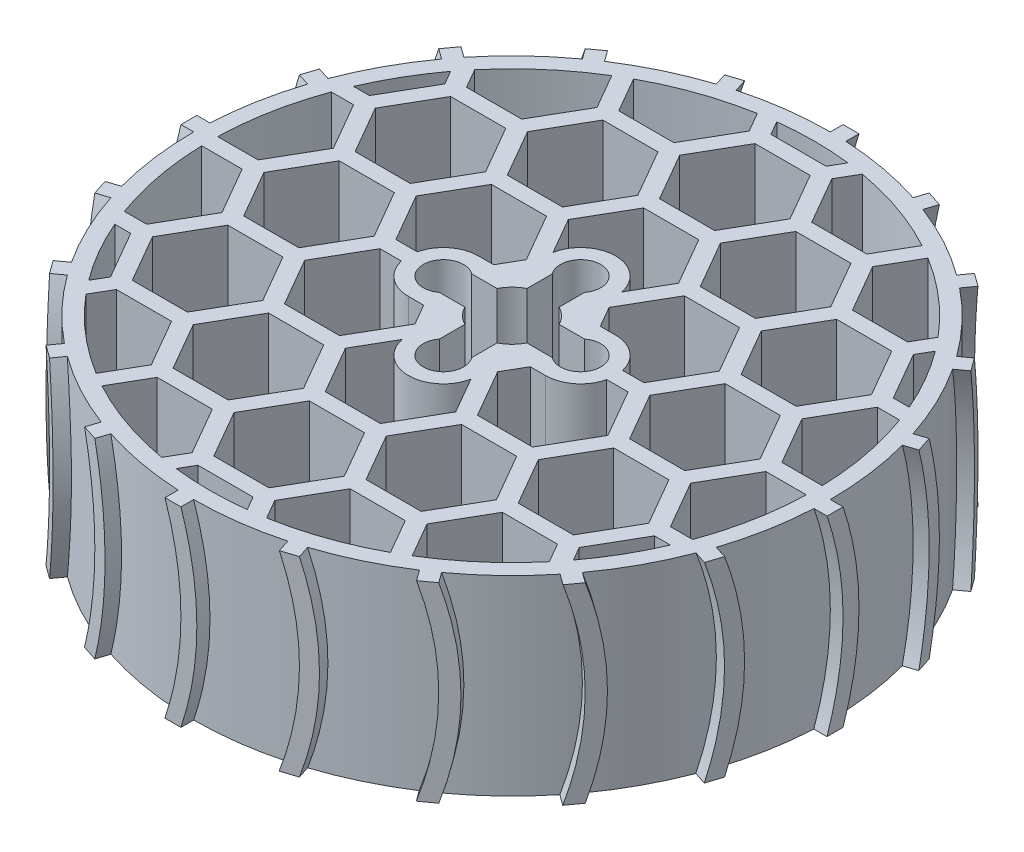
SolidWorks part; units mm, degrees
ref_plane "Front Plane" through (0, 0, 0) normal (0, 0, 1) x (1, 0, 0)
ref_plane "Top Plane" through (0, 0, 0) normal (0, 1, 0) x (1, 0, 0)
ref_plane "Right Plane" through (0, 0, 0) normal (1, 0, 0) x (0, 0, -1)
sketch "Sketch1" plane through (0, 0, 0) normal (0, 1, 0) x (1, 0, 0)
  line L0 (-17.7275, -5.0583) -> (-9.768, -5.0583)
  line L1 (-17.7275, 5.0583) -> (-9.768, 5.0583)
  line L2 (-21.548, 11) -> (-11, 11)
  line L3 (-21.548, -11) -> (-11, -11)
  line L4 (-11, 21.548) -> (-11, 11)
  line L5 (11, 21.548) -> (11, 11)
  line L6 (5.0583, 17.7275) -> (5.0583, 9.768)
  line L7 (-5.0583, 17.7275) -> (-5.0583, 9.768)
  line L8 (21.548, 11) -> (11, 11)
  line L9 (21.548, -11) -> (11, -11)
  line L10 (17.7275, -5.0583) -> (9.768, -5.0583)
  line L11 (17.7275, 5.0583) -> (9.768, 5.0583)
  line L12 (11, -21.548) -> (11, -11)
  line L13 (-11, -21.548) -> (-11, -11)
  line L14 (-5.0583, -17.7275) -> (-5.0583, -9.768)
  line L15 (5.0583, -17.7275) -> (5.0583, -9.768)
  line L16 (-21.548, 0) -> (21.548, 0) construction
  arc A0 (-9.768, -5.0583) -> (-5.0583, -9.768) centre (0, 0) ccw
  arc A1 (-21.548, 11) -> (-21.548, -11) centre (-21.548, 0) ccw
  arc A5 (-5.0583, 9.768) -> (-9.768, 5.0583) centre (0, 0) ccw
  circle A6 centre (-21.548, 0) radius 3.302
  circle A7 centre (-21.548, 0) radius 6.339
  circle A8 centre (0, 0) radius 11 construction
  arc A9 (11, 21.548) -> (-11, 21.548) centre (0, 21.548) ccw
  circle A10 centre (0, 21.548) radius 6.339
  circle A11 centre (0, 21.548) radius 3.302
  arc A12 (21.548, -11) -> (21.548, 11) centre (21.548, 0) ccw
  circle A13 centre (21.548, 0) radius 6.339
  circle A14 centre (21.548, 0) radius 3.302
  arc A15 (-11, -21.548) -> (11, -21.548) centre (0, -21.548) ccw
  circle A16 centre (0, -21.548) radius 6.339
  circle A17 centre (0, -21.548) radius 3.302
  arc A18 (-5.0583, 9.768) -> (-9.768, 5.0583) centre (0, 0) ccw
  arc A19 (9.768, 5.0583) -> (5.0583, 9.768) centre (0, 0) ccw
  arc A20 (5.0583, -9.768) -> (9.768, -5.0583) centre (0, 0) ccw
  arc A21 (-9.768, -5.0583) -> (-5.0583, -9.768) centre (0, 0) ccw
  point P60 (0, 0)
  dimension "D1" = 6.604
  dimension "D2" = 12.678
  dimension "D3" = 22
  dimension "D4" = 11
  dimension "D7" = 4
  dimension "D5" = 10.548
  dimension "D6" = 7.9595
  dimension "D8" = 21.548
  dimension "D9" = 5.0583
  dimension "D10" = 5.0583
  dimension "D11" = 10.1166
sketch "Sketch3" plane through (0, 0, 0) normal (0, 1, 0) x (1, 0, 0)
  line L0 (0, 0) -> (17.3205, 0) construction
  line L1 (8.6603, 15) -> (-8.6603, 15) construction
  line L2 (-8.6603, 15) -> (-17.3205, 0) construction
  line L3 (-17.3205, 0) -> (-8.6603, -15) construction
  line L4 (-8.6603, -15) -> (8.6603, -15) construction
  line L5 (8.6603, -15) -> (17.3205, 0) construction
  line L6 (17.3205, 0) -> (8.6603, 15) construction
  line L7 (38.9711, 32.5) -> (21.6506, 32.5)
  line L8 (21.6506, 32.5) -> (12.9904, 17.5)
  line L9 (12.9904, 17.5) -> (16.7432, 11)
  line L11 (38.9711, 2.5) -> (47.6314, 17.5)
  line L12 (47.6314, 17.5) -> (38.9711, 32.5)
  line L13 (69.282, 50) -> (51.9615, 50)
  line L14 (51.9615, 50) -> (43.3013, 35)
  line L15 (43.3013, 35) -> (51.9615, 20)
  line L16 (51.9615, 20) -> (69.282, 20)
  line L17 (69.282, 20) -> (77.9423, 35)
  line L18 (77.9423, 35) -> (69.282, 50)
  line L21 (73.6122, 52.5) -> (82.2724, 37.5)
  line L22 (82.2724, 37.5) -> (87.2855, 37.5)
  line L25 (38.9711, -2.5) -> (32.2601, -2.5)
  line L27 (12.9904, -17.5) -> (21.6506, -32.5)
  line L28 (21.6506, -32.5) -> (38.9711, -32.5)
  line L29 (38.9711, -32.5) -> (47.6314, -17.5)
  line L30 (47.6314, -17.5) -> (38.9711, -2.5)
  line L31 (69.282, 15) -> (51.9615, 15)
  line L32 (51.9615, 15) -> (43.3013, 0)
  line L33 (43.3013, 0) -> (51.9615, -15)
  line L34 (51.9615, -15) -> (69.282, -15)
  line L35 (69.282, -15) -> (77.9423, 0)
  line L36 (77.9423, 0) -> (69.282, 15)
  line L37 (89.2679, 32.5) -> (82.2724, 32.5)
  line L38 (82.2724, 32.5) -> (73.6122, 17.5)
  line L39 (73.6122, 17.5) -> (82.2724, 2.5)
  line L40 (82.2724, 2.5) -> (94.9671, 2.5)
  line L43 (38.9711, -37.5) -> (21.6506, -37.5)
  line L44 (21.6506, -37.5) -> (12.9904, -52.5)
  line L45 (12.9904, -52.5) -> (21.6506, -67.5)
  line L46 (21.6506, -67.5) -> (38.9711, -67.5)
  line L47 (38.9711, -67.5) -> (47.6314, -52.5)
  line L48 (47.6314, -52.5) -> (38.9711, -37.5)
  line L49 (69.282, -20) -> (51.9615, -20)
  line L50 (51.9615, -20) -> (43.3013, -35)
  line L51 (43.3013, -35) -> (51.9615, -50)
  line L52 (51.9615, -50) -> (69.282, -50)
  line L53 (69.282, -50) -> (77.9423, -35)
  line L54 (77.9423, -35) -> (69.282, -20)
  line L55 (94.9671, -2.5) -> (82.2724, -2.5)
  line L56 (82.2724, -2.5) -> (73.6122, -17.5)
  line L57 (73.6122, -17.5) -> (82.2724, -32.5)
  line L58 (82.2724, -32.5) -> (89.2679, -32.5)
  line L61 (38.9711, -72.5) -> (21.6506, -72.5)
  line L62 (21.6506, -72.5) -> (12.9904, -87.5)
  line L63 (12.9904, -87.5) -> (16.4881, -93.5582)
  line L66 (45.3185, -83.4939) -> (38.9711, -72.5)
  line L67 (69.282, -55) -> (51.9615, -55)
  line L68 (51.9615, -55) -> (43.3013, -70)
  line L69 (43.3013, -70) -> (49.6486, -80.9939)
  line L72 (72.7798, -61.0582) -> (69.282, -55)
  line L73 (87.2855, -37.5) -> (82.2724, -37.5)
  line L74 (82.2724, -37.5) -> (73.6122, -52.5)
  line L75 (73.6122, -52.5) -> (76.1187, -56.8414)
  line L80 (-10.7898, -23.6884) -> (-17.3205, -35)
  line L81 (-17.3205, -35) -> (-8.6603, -50)
  line L82 (-8.6603, -50) -> (8.6603, -50)
  line L83 (8.6603, -50) -> (17.3205, -35)
  line L84 (17.3205, -35) -> (10.7898, -23.6884)
  line L85 (8.6603, -55) -> (-8.6603, -55)
  line L86 (-8.6603, -55) -> (-17.3205, -70)
  line L87 (-17.3205, -70) -> (-8.6603, -85)
  line L88 (-8.6603, -85) -> (8.6603, -85)
  line L89 (8.6603, -85) -> (17.3205, -70)
  line L90 (17.3205, -70) -> (8.6603, -55)
  line L91 (8.6603, -90) -> (-8.6603, -90)
  line L92 (-8.6603, -90) -> (-11.1668, -94.3414)
  line L97 (0, 0) -> (77.9423, -45) construction
  line L98 (-21.6506, 32.5) -> (-38.9711, 32.5)
  line L99 (-38.9711, 32.5) -> (-47.6314, 17.5)
  line L100 (-47.6314, 17.5) -> (-38.9711, 2.5)
  line L101 (-38.9711, 2.5) -> (-32.2601, 2.5)
  line L103 (-12.9904, 17.5) -> (-21.6506, 32.5)
  line L104 (-51.9615, 50) -> (-69.282, 50)
  line L105 (-69.282, 50) -> (-77.9423, 35)
  line L106 (-77.9423, 35) -> (-69.282, 20)
  line L107 (-69.282, 20) -> (-51.9615, 20)
  line L108 (-51.9615, 20) -> (-43.3013, 35)
  line L109 (-43.3013, 35) -> (-51.9615, 50)
  line L113 (-87.2855, 37.5) -> (-82.2724, 37.5)
  line L114 (-82.2724, 37.5) -> (-73.6122, 52.5)
  line L115 (-73.6122, 52.5) -> (-76.1187, 56.8414)
  line L116 (-21.6506, 67.5) -> (-38.9711, 67.5)
  line L117 (-38.9711, 67.5) -> (-47.6314, 52.5)
  line L118 (-47.6314, 52.5) -> (-38.9711, 37.5)
  line L119 (-38.9711, 37.5) -> (-21.6506, 37.5)
  line L120 (-21.6506, 37.5) -> (-12.9904, 52.5)
  line L121 (-12.9904, 52.5) -> (-21.6506, 67.5)
  line L124 (-72.7798, 61.0582) -> (-69.282, 55)
  line L125 (-69.282, 55) -> (-51.9615, 55)
  line L126 (-51.9615, 55) -> (-43.3013, 70)
  line L127 (-43.3013, 70) -> (-49.6486, 80.9939)
  line L128 (-82.2724, 102.5) -> (-99.5929, 102.5) [skipped]
  line L129 (-99.5929, 102.5) -> (-108.2532, 87.5) [skipped]
  line L130 (-108.2532, 87.5) -> (-99.5929, 72.5) [skipped]
  line L131 (-99.5929, 72.5) -> (-82.2724, 72.5) [skipped]
  line L132 (-82.2724, 72.5) -> (-73.6122, 87.5) [skipped]
  line L133 (-73.6122, 87.5) -> (-82.2724, 102.5) [skipped]
  line L136 (-45.3185, 83.4939) -> (-38.9711, 72.5)
  line L137 (-38.9711, 72.5) -> (-21.6506, 72.5)
  line L138 (-21.6506, 72.5) -> (-12.9904, 87.5)
  line L139 (-12.9904, 87.5) -> (-16.4881, 93.5582)
  line L140 (-51.9615, 120) -> (-69.282, 120) [skipped]
  line L141 (-69.282, 120) -> (-77.9423, 105) [skipped]
  line L142 (-77.9423, 105) -> (-69.282, 90) [skipped]
  line L143 (-69.282, 90) -> (-51.9615, 90) [skipped]
  line L144 (-51.9615, 90) -> (-43.3013, 105) [skipped]
  line L145 (-43.3013, 105) -> (-51.9615, 120) [skipped]
  line L146 (-82.2724, 137.5) -> (-99.5929, 137.5) [skipped]
  line L147 (-99.5929, 137.5) -> (-108.2532, 122.5) [skipped]
  line L148 (-108.2532, 122.5) -> (-99.5929, 107.5) [skipped]
  line L149 (-99.5929, 107.5) -> (-82.2724, 107.5) [skipped]
  line L150 (-82.2724, 107.5) -> (-73.6122, 122.5) [skipped]
  line L151 (-73.6122, 122.5) -> (-82.2724, 137.5) [skipped]
  line L152 (-21.6506, 137.5) -> (-38.9711, 137.5) [skipped]
  line L153 (-38.9711, 137.5) -> (-47.6314, 122.5) [skipped]
  line L154 (-47.6314, 122.5) -> (-38.9711, 107.5) [skipped]
  line L155 (-38.9711, 107.5) -> (-21.6506, 107.5) [skipped]
  line L156 (-21.6506, 107.5) -> (-12.9904, 122.5) [skipped]
  line L157 (-12.9904, 122.5) -> (-21.6506, 137.5) [skipped]
  line L158 (-51.9615, 155) -> (-69.282, 155) [skipped]
  line L159 (-69.282, 155) -> (-77.9423, 140) [skipped]
  line L160 (-77.9423, 140) -> (-69.282, 125) [skipped]
  line L161 (-69.282, 125) -> (-51.9615, 125) [skipped]
  line L162 (-51.9615, 125) -> (-43.3013, 140) [skipped]
  line L163 (-43.3013, 140) -> (-51.9615, 155) [skipped]
  line L164 (-82.2724, 172.5) -> (-99.5929, 172.5) [skipped]
  line L165 (-99.5929, 172.5) -> (-108.2532, 157.5) [skipped]
  line L166 (-108.2532, 157.5) -> (-99.5929, 142.5) [skipped]
  line L167 (-99.5929, 142.5) -> (-82.2724, 142.5) [skipped]
  line L168 (-82.2724, 142.5) -> (-73.6122, 157.5) [skipped]
  line L169 (-73.6122, 157.5) -> (-82.2724, 172.5) [skipped]
  line L170 (8.6603, 50) -> (-8.6603, 50)
  line L171 (-8.6603, 50) -> (-17.3205, 35)
  line L172 (-17.3205, 35) -> (-10.7898, 23.6884)
  line L174 (10.7898, 23.6884) -> (17.3205, 35)
  line L175 (17.3205, 35) -> (8.6603, 50)
  line L176 (8.6603, 85) -> (-8.6603, 85)
  line L177 (-8.6603, 85) -> (-17.3205, 70)
  line L178 (-17.3205, 70) -> (-8.6603, 55)
  line L179 (-8.6603, 55) -> (8.6603, 55)
  line L180 (8.6603, 55) -> (17.3205, 70)
  line L181 (17.3205, 70) -> (8.6603, 85)
  line L184 (-11.1668, 94.3414) -> (-8.6603, 90)
  line L185 (-8.6603, 90) -> (8.6603, 90)
  line L186 (8.6603, 90) -> (11.1668, 94.3414)
  line L188 (0, 0) -> (-77.9423, 45) construction
  line L189 (-51.9615, 15) -> (-69.282, 15)
  line L190 (-69.282, 15) -> (-77.9423, 0)
  line L191 (-77.9423, 0) -> (-69.282, -15)
  line L192 (-69.282, -15) -> (-51.9615, -15)
  line L193 (-51.9615, -15) -> (-43.3013, 0)
  line L194 (-43.3013, 0) -> (-51.9615, 15)
  line L195 (-82.2724, -2.5) -> (-94.9671, -2.5)
  line L198 (-89.2679, -32.5) -> (-82.2724, -32.5)
  line L199 (-82.2724, -32.5) -> (-73.6122, -17.5)
  line L200 (-73.6122, -17.5) -> (-82.2724, -2.5)
  line L201 (-51.9615, -20) -> (-69.282, -20)
  line L202 (-69.282, -20) -> (-77.9423, -35)
  line L203 (-77.9423, -35) -> (-69.282, -50)
  line L204 (-69.282, -50) -> (-51.9615, -50)
  line L205 (-51.9615, -50) -> (-43.3013, -35)
  line L206 (-43.3013, -35) -> (-51.9615, -20)
  line L207 (-82.2724, -37.5) -> (-87.2855, -37.5)
  line L211 (-76.1187, -56.8414) -> (-73.6122, -52.5)
  line L212 (-73.6122, -52.5) -> (-82.2724, -37.5)
  line L213 (-51.9615, -55) -> (-69.282, -55)
  line L214 (-69.282, -55) -> (-72.7798, -61.0582)
  line L217 (-49.6486, -80.9939) -> (-43.3013, -70)
  line L218 (-43.3013, -70) -> (-51.9615, -55)
  line L219 (-82.2724, -72.5) -> (-99.5929, -72.5) [skipped]
  line L220 (-99.5929, -72.5) -> (-108.2532, -87.5) [skipped]
  line L221 (-108.2532, -87.5) -> (-99.5929, -102.5) [skipped]
  line L222 (-99.5929, -102.5) -> (-82.2724, -102.5) [skipped]
  line L224 (-73.6122, -87.5) -> (-82.2724, -72.5) [skipped]
  line L225 (-51.9615, -90) -> (-69.282, -90) [skipped]
  line L226 (-69.282, -90) -> (-77.9423, -105) [skipped]
  line L227 (-77.9423, -105) -> (-69.282, -120) [skipped]
  line L228 (-69.282, -120) -> (-51.9615, -120) [skipped]
  line L230 (-43.3013, -105) -> (-51.9615, -90) [skipped]
  line L231 (-82.2724, -107.5) -> (-99.5929, -107.5) [skipped]
  line L232 (-99.5929, -107.5) -> (-108.2532, -122.5) [skipped]
  line L233 (-108.2532, -122.5) -> (-99.5929, -137.5) [skipped]
  line L234 (-99.5929, -137.5) -> (-82.2724, -137.5) [skipped]
  line L236 (-73.6122, -122.5) -> (-82.2724, -107.5) [skipped]
  line L238 (-38.9711, -2.5) -> (-47.6314, -17.5)
  line L239 (-47.6314, -17.5) -> (-38.9711, -32.5)
  line L240 (-38.9711, -32.5) -> (-21.6506, -32.5)
  line L241 (-21.6506, -32.5) -> (-12.9904, -17.5)
  line L242 (-12.9904, -17.5) -> (-16.7432, -11)
  line L243 (-21.6506, -37.5) -> (-38.9711, -37.5)
  line L244 (-38.9711, -37.5) -> (-47.6314, -52.5)
  line L245 (-47.6314, -52.5) -> (-38.9711, -67.5)
  line L246 (-38.9711, -67.5) -> (-21.6506, -67.5)
  line L247 (-21.6506, -67.5) -> (-12.9904, -52.5)
  line L248 (-12.9904, -52.5) -> (-21.6506, -37.5)
  line L249 (-21.6506, -72.5) -> (-38.9711, -72.5)
  line L250 (-38.9711, -72.5) -> (-45.3185, -83.4939)
  line L254 (-12.9904, -87.5) -> (-21.6506, -72.5)
  line L255 (-21.6506, 32.5) -> (-51.9615, 15) construction
  line L256 (-21.6506, 32.5) -> (-21.6506, 3.3004) construction
  line L257 (-16.4881, -93.5582) -> (-12.9904, -87.5)
  line L258 (76.1187, 56.8414) -> (73.6122, 52.5)
  line L259 (8.6603, 55) -> (51.9615, 50) construction
  line L260 (-94.9671, 2.5) -> (-82.2724, 2.5)
  line L261 (-82.2724, 2.5) -> (-73.6122, 17.5)
  line L262 (-73.6122, 17.5) -> (-82.2724, 32.5)
  line L263 (-82.2724, 32.5) -> (-89.2679, 32.5)
  line L266 (60.6218, 50) -> (60.6218, 79.5299) construction
  line L267 (17.3205, 35) -> (43.3013, 70) construction
  line L269 (49.6486, 80.9939) -> (43.3013, 70)
  line L270 (43.3013, 70) -> (51.9615, 55)
  line L271 (51.9615, 55) -> (69.282, 55)
  line L272 (69.282, 55) -> (72.7798, 61.0582)
  line L274 (51.9615, 85) -> (8.6603, 90) construction
  line L275 (21.6506, 37.5) -> (38.9711, 37.5)
  line L276 (38.9711, 37.5) -> (47.6314, 52.5)
  line L277 (47.6314, 52.5) -> (38.9711, 67.5)
  line L278 (38.9711, 67.5) -> (21.6506, 67.5)
  line L279 (21.6506, 67.5) -> (12.9904, 52.5)
  line L280 (12.9904, 52.5) -> (21.6506, 37.5)
  line L281 (43.3013, 70) -> (21.3703, 99.5443) construction
  line L282 (-69.282, 50) -> (-51.9615, 20) construction
  line L285 (12.9904, 87.5) -> (21.6506, 72.5)
  line L286 (21.6506, 72.5) -> (38.9711, 72.5)
  line L287 (38.9711, 72.5) -> (45.3185, 83.4939)
  line L289 (-8.6603, 120) -> (-17.3205, 105) [skipped]
  line L290 (8.6603, 120) -> (-8.6603, 120) [skipped]
  line L291 (17.3205, 105) -> (8.6603, 120) [skipped]
  line L292 (-21.6506, 102.5) -> (-38.9711, 102.5) [skipped]
  line L293 (-47.273, 88.1207) -> (-47.6314, 87.5) [skipped]
  line L294 (-52.6783, 85) -> (-69.282, 85) [skipped]
  line L295 (-69.282, 85) -> (-77.9423, 70) [skipped]
  line L296 (-82.2724, 67.5) -> (-99.5929, 67.5) [skipped]
  line L297 (-99.5929, 67.5) -> (-108.2532, 52.5) [skipped]
  line L298 (-108.2532, 52.5) -> (-99.5929, 37.5) [skipped]
  line L299 (-103.923, 25) -> (-108.2532, 17.5) [skipped]
  line L300 (-51.9615, 50) -> (-69.282, 20) construction
  line L301 (11.1668, -94.3414) -> (8.6603, -90)
  line L302 (-99.9513, 3.1207) -> (-99.5929, 2.5) [skipped]
  line L303 (-108.2532, -17.5) -> (-99.5929, -32.5) [skipped]
  line L304 (-99.5929, -2.5) -> (-99.9513, -3.1207) [skipped]
  line L305 (-99.5929, -37.5) -> (-108.2532, -52.5) [skipped]
  line L306 (-108.2532, -52.5) -> (-99.5929, -67.5) [skipped]
  line L307 (-99.5929, -67.5) -> (-82.2724, -67.5) [skipped]
  line L308 (-77.9423, -70) -> (-69.282, -85) [skipped]
  line L309 (-52.6783, -85) -> (-51.9615, -85) [skipped]
  line L310 (-47.273, -88.1207) -> (-38.9711, -102.5) [skipped]
  line L312 (-38.9711, -102.5) -> (-21.6506, -102.5) [skipped]
  line L313 (17.3205, -105) -> (13.8753, -99.0327) [skipped]
  line L314 (8.6603, -120) -> (17.3205, -105) [skipped]
  line L315 (-8.6603, -120) -> (8.6603, -120) [skipped]
  line L316 (-17.3205, -105) -> (-8.6603, -120) [skipped]
  line L317 (21.6506, -102.5) -> (38.9711, -102.5) [skipped]
  line L318 (47.273, -88.1207) -> (47.6314, -87.5) [skipped]
  line L319 (52.6783, -85) -> (69.282, -85) [skipped]
  line L320 (69.282, -85) -> (77.9423, -70) [skipped]
  line L321 (82.2724, -67.5) -> (99.5929, -67.5) [skipped]
  line L322 (99.5929, -67.5) -> (103.923, -60) [skipped]
  line L323 (108.2532, -52.5) -> (99.5929, -37.5) [skipped]
  line L324 (99.5929, -32.5) -> (108.2532, -17.5) [skipped]
  line L325 (99.9513, -3.1207) -> (99.5929, -2.5) [skipped]
  line L326 (99.9513, 3.1207) -> (108.2532, 17.5) [skipped]
  line L327 (108.2532, 17.5) -> (99.5929, 32.5) [skipped]
  line L328 (82.2724, 67.5) -> (78.8272, 61.5327) [skipped]
  line L329 (99.5929, 67.5) -> (82.2724, 67.5) [skipped]
  line L330 (108.2532, 52.5) -> (99.5929, 67.5) [skipped]
  line L331 (99.5929, 37.5) -> (108.2532, 52.5) [skipped]
  line L332 (30.3109, 102.5) -> (21.6506, 102.5) [skipped]
  line L333 (16.4881, 93.5582) -> (12.9904, 87.5)
  line L334 (21.6506, 102.5) -> (20.5681, 100.625) [skipped]
  line L335 (47.6314, 87.5) -> (47.273, 88.1207) [skipped]
  line L336 (-17.7275, -5.0583) -> (-9.768, -5.0583)
  line L337 (69.282, 85) -> (60.6218, 85) [skipped]
  line L338 (73.6122, 77.5) -> (69.282, 85) [skipped]
  line L339 (-17.7275, 5.0583) -> (-9.768, 5.0583)
  line L340 (-21.548, 11) -> (-11, 11)
  line L341 (-21.548, -11) -> (-11, -11)
  line L342 (-11, 21.548) -> (-11, 11)
  line L343 (11, 21.548) -> (11, 11)
  line L344 (5.0583, 17.7275) -> (5.0583, 9.768)
  line L345 (-5.0583, 17.7275) -> (-5.0583, 9.768)
  line L346 (21.548, 11) -> (11, 11)
  line L347 (21.548, -11) -> (11, -11)
  line L348 (17.7275, -5.0583) -> (9.768, -5.0583)
  line L349 (17.7275, 5.0583) -> (9.768, 5.0583)
  line L350 (11, -21.548) -> (11, -11)
  line L351 (-11, -21.548) -> (-11, -11)
  line L352 (-5.0583, -17.7275) -> (-5.0583, -9.768)
  line L353 (5.0583, -17.7275) -> (5.0583, -9.768)
  line L354 (-21.548, 0) -> (21.548, 0) construction
  line L355 (-16.7432, 11) -> (-12.9904, 17.5)
  line L356 (-21.6506, 2.5) -> (-21.1983, 3.2834) [skipped]
  line L357 (-32.2601, -2.5) -> (-38.9711, -2.5)
  line L358 (-21.6506, -2.5) -> (-23.7051, -2.5) [skipped]
  line L359 (8.6603, -20) -> (6.1471, -20) [skipped]
  line L360 (16.7432, -11) -> (12.9904, -17.5)
  line L361 (21.1983, -3.2834) -> (19.6095, -6.0353) [skipped]
  line L363 (32.2601, 2.5) -> (38.9711, 2.5)
  line L364 (21.6506, 2.5) -> (23.7051, 2.5) [skipped]
  line L365 (-8.6603, 20) -> (-6.1471, 20) [skipped]
  circle A0 centre (0, 0) radius 15 construction
  circle A1 centre (0, 0) radius 100
  circle A2 centre (0, 0) radius 95
  circle A3 centre (-90.9327, 17.5) radius 15 construction
  circle A4 centre (60.6218, 70) radius 15 construction
  circle A5 centre (30.3109, 52.5) radius 15 construction
  circle A6 centre (30.3109, 87.5) radius 15 construction
  arc A7 (-9.768, -5.0583) -> (-5.0583, -9.768) centre (0, 0) ccw
  arc A8 (-21.548, 11) -> (-21.548, -11) centre (-21.548, 0) ccw
  arc A9 (-5.0583, 9.768) -> (-9.768, 5.0583) centre (0, 0) ccw
  circle A10 centre (-21.548, 0) radius 3.302
  circle A11 centre (-21.548, 0) radius 6.339
  circle A12 centre (0, 0) radius 11 construction
  arc A13 (11, 21.548) -> (-11, 21.548) centre (0, 21.548) ccw
  circle A14 centre (0, 21.548) radius 6.339
  circle A15 centre (0, 21.548) radius 3.302
  arc A16 (21.548, -11) -> (21.548, 11) centre (21.548, 0) ccw
  circle A17 centre (21.548, 0) radius 6.339
  circle A18 centre (21.548, 0) radius 3.302
  arc A19 (-11, -21.548) -> (11, -21.548) centre (0, -21.548) ccw
  circle A20 centre (0, -21.548) radius 6.339
  circle A21 centre (0, -21.548) radius 3.302
  arc A22 (-5.0583, 9.768) -> (-9.768, 5.0583) centre (0, 0) ccw
  arc A23 (9.768, 5.0583) -> (5.0583, 9.768) centre (0, 0) ccw
  arc A24 (5.0583, -9.768) -> (9.768, -5.0583) centre (0, 0) ccw
  arc A25 (-9.768, -5.0583) -> (-5.0583, -9.768) centre (0, 0) ccw
  point P143 (-90.9327, 17.5)
  point P418 (0, 0)
  dimension "D2" = 200
  dimension "D3" = 190
  dimension "D19" = 6.604
  dimension "D21" = 12.678
  dimension "D24" = 22
  dimension "D29" = 11
  dimension "D1" = 30
  dimension "D6" = 5
  dimension "D12" = 3
  dimension "D14" = 60
  dimension "D16" = 5
  dimension "D17" = 30
  dimension "D18" = 60
  dimension "D20" = 5
  dimension "D22" = 30
  dimension "D23" = 5
  dimension "D25" = 120
  dimension "D26" = 35
  dimension "D27" = 90
  dimension "D28" = 30
  dimension "D30" = 10.548
  dimension "D31" = 7.9595
  dimension "D32" = 21.548
  dimension "D33" = 5.0583
  dimension "D34" = 5.0583
  dimension "D35" = 10.1166
  dimension "D4" = 4
  dimension "D5" = 4
  dimension "D8" = 4
  dimension "D9" = 4
  dimension "D13" = 4
extrude "Boss-Extrude1" add sketch "Sketch3" along normal blind 30 contours A14 A15 | A17 A18 | A20 A21 | A11 A10 region at (-27.7077, 0, 0) region at (0, 0, 15.3883) region at (-5.5551, 0, -18.8866) region at (15.3883, 0, 0)
extrude "Boss-Extrude2" add sketch "Sketch3<3>" along normal blind 60 contours A1 A2 | L301 A2 L63 L62 L61 L66 L69 L68 L67 L72 L75 L74 L73 L58 L57 L56 L55 L40 L39 L38 L37 L22 L21 L258 L272 L271 L270 L269 L287 L286 L285 L333 L186 L185 L184 L139 L138 L137 L136 L127 L126 | A19 L350 L347 A16 L346 L343 A13 L342 L340 A8 L341 L351 A24 L353 A20 L352 A7 L336 A11 L339 A9 L345 A14 L344 A23 L349 A17 L348 region at (19.1456, 0, -10.0794) region at (75.6233, 0, -43.6611) region at (97.1597, 0, 1.5164)
sketch "Sketch3<3>" plane through (0, 0, 0) normal (0, 1, 0) x (1, 0, 0) same geometry as "Sketch3"
ref_plane "Plane1" through (-100, 0, 0) normal (-1, 0, 0) x (0, 0, 1)
sketch "Sketch4" plane through (-100, 0, 0) normal (-1, 0, 0) x (0, 0, 1)
  line L0 (0, 0) -> (0, 60) construction
  line L1 (100, 60) -> (-100, 60) construction
  line L2 (0, 30) -> (5, 30) construction
  line L3 (0, 30) -> (-5, 30) construction
  line L5 (-5, 30) -> (-5, 60) construction
  line L6 (-5, 60) -> (-5.0583, 0) construction
  line L7 (-5, 60) -> (0, 60)
  line L8 (-5.0583, 0) -> (0, 0)
  spline S0 degree 2 poles (0, 60) (10, 30) (0, 0) knots 0 0 0 1 1 1
  spline S1 degree 2 poles (-5.0583, 0) (5.0291, 29.9905) (-5, 60) knots 0 0 0 1 1 1
  dimension "D1" = 5
  dimension "D2" = 5
extrude "Boss-Extrude3" add sketch "Sketch4" along normal blind 4 and the other way blind 3
pattern_circular "CirPattern1" count 20 over 360 about axis through (0, 60, 0) along (0, -1, 0) of "Boss-Extrude3"
